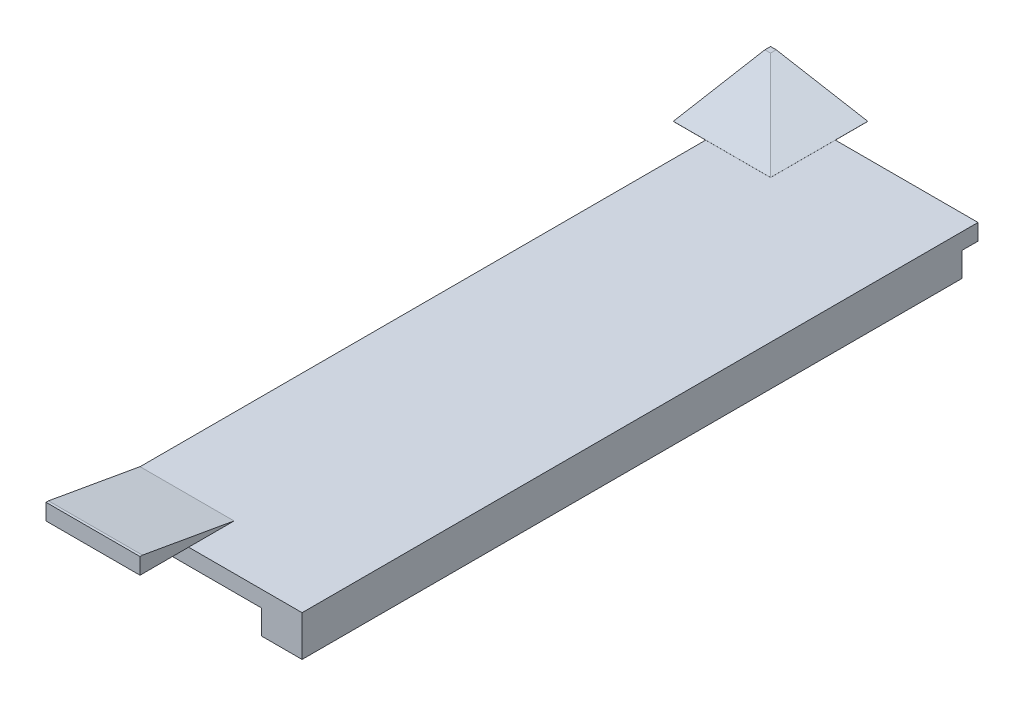
SolidWorks part; units mm, degrees
ref_plane "Front Plane" through (0, 0, 0) normal (0, 0, 1) x (1, 0, 0)
ref_plane "Top Plane" through (0, 0, 0) normal (0, 1, 0) x (1, 0, 0)
ref_plane "Right Plane" through (0, 0, 0) normal (1, 0, 0) x (0, 0, -1)
sketch "Sketch1" plane through (0, 0, 0) normal (0, 1, 0) x (1, 0, 0)
  line L1 (0, 0) -> (25.6, 0)
  line L2 (0, 0) -> (0, 83.4)
  line L3 (0, 83.4) -> (25.6, 83.4)
  line L4 (25.6, 0) -> (25.6, 83.4)
  dimension "D1" = 83.4
  dimension "D2" = 25.6
extrude "Boss-Extrude1" add sketch "Sketch1" along normal blind 2
sketch "Sketch2" plane through (0, 2, 0) normal (0, 1, 0) x (1, 0, 0)
  line L0 (0, 83.4) -> (0, 0) construction
  line L1 (0, 5.6) -> (11.6, 5.6)
  line L2 (0, 5.6) -> (0, -6)
  line L3 (0, -6) -> (11.6, -6)
  line L4 (11.6, 5.6) -> (11.6, -6)
  line L5 (25.6, 83.4) -> (0, 83.4) construction
  line L6 (0, 0) -> (25.6, 0) construction
  line L7 (8, 75.4) -> (-4, 75.4)
  line L8 (8, 75.4) -> (8, 87.4)
  line L9 (8, 87.4) -> (-4, 87.4)
  line L10 (-4, 75.4) -> (-4, 87.4)
  dimension "D1" = 11.6
  dimension "D2" = 6
  dimension "D3" = 5.6
  dimension "D4" = 8
  dimension "D5" = 8
  dimension "D6" = 4
  dimension "D7" = 4
extrude "Boss-Extrude2" add sketch "Sketch2" along normal blind 2
chamfer "Chamfer1" distance 11.3 angle 10 3 edges at (5.8, 4, -5.6) (8, 4, -81.4) (2, 4, -75.4) first distance on face at (5.8, 4, 0.2) first distance on face at (2, 4, -81.4)
sketch "Sketch4" plane through (0, 0, 0) normal (0, -1, 0) x (1, 0, 0)
  line L0 (25.6, -83.4) -> (0, -83.4) construction
  line L1 (25.6, -81.4) -> (20.6, -81.4)
  line L2 (25.6, -81.4) -> (25.6, 0)
  line L3 (25.6, 0) -> (20.6, 0)
  line L4 (20.6, -81.4) -> (20.6, 0)
  point P5 (0, 0)
  point P6 (0, 0)
  dimension "D1" = 81.4
  dimension "D2" = 5
  dimension "D3" = 2
extrude "Boss-Extrude3" add sketch "Sketch4" along normal blind 3
